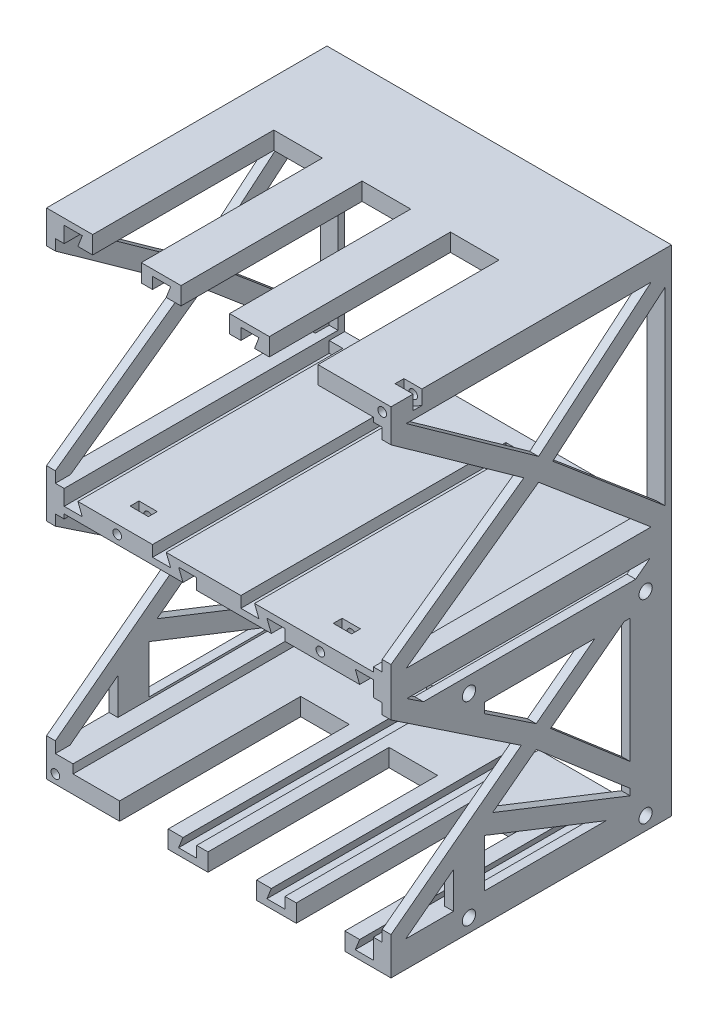
SolidWorks part; units mm, degrees
ref_plane "Front Plane" through (0, 0, 0) normal (0, 0, 1) x (1, 0, 0)
ref_plane "Top Plane" through (0, 0, 0) normal (0, 1, 0) x (1, 0, 0)
ref_plane "Right Plane" through (0, 0, 0) normal (1, 0, 0) x (0, 0, -1)
sketch "Bounds" plane through (0, 0, 0) normal (0, 0, 1) x (1, 0, 0)
  line L0 (-39, 56) -> (39, -56) construction
  line L1 (-39, 56) -> (39, 56)
  line L2 (-39, 56) -> (-39, -56)
  line L3 (-39, -56) -> (39, -56)
  line L4 (39, 56) -> (39, -56)
  line L5 (0, 50) -> (0, -50) construction
  line L6 (0, 0) -> (-66.1927, 0) construction
  line L7 (-35, 52) -> (35, 52)
  line L8 (35, 52) -> (35, -52)
  line L9 (-35, -52) -> (35, -52)
  line L10 (-35, 52) -> (-35, -52)
  dimension "D1" = 112
  dimension "D2" = 78
  dimension "D3" = 4
extrude "Boss-Extrude3" add sketch "Bounds" along normal blind 63.5
sketch "Sketch10" plane through (0, 0, 0) normal (0, 0, 1) x (1, 0, 0)
  line L0 (-26.7546, 0) -> (11.5824, 0) construction
  line L1 (-35, 2) -> (35, 2)
  line L2 (-35, 52) -> (-35, -52) construction
  line L3 (35, -52) -> (35, 52) construction
  line L4 (-35, -2) -> (35, -2)
  line L5 (35, 2) -> (35, -2)
  line L6 (-35, 2) -> (-35, -2)
  dimension "D1" = 2
extrude "Boss-Extrude4" add sketch "Sketch10" along normal up to surface (63.5 mm away) up to face at (0, 0, 63.5)
sketch "Placement" plane through (0, 0, 63.5) normal (0, 0, 1) x (1, 0, 0)
  line L0 (35, 2) -> (-35, 2) construction
  line L1 (-35, 52) -> (-15, 52)
  line L2 (-35, 52) -> (-35, 2)
  line L3 (-35, 2) -> (-15, 2)
  line L4 (-15, 52) -> (-15, 2)
  line L13 (-35, -52) -> (35, -52) construction
  line L14 (35, -2) -> (15, -2)
  line L15 (35, -2) -> (35, -52)
  line L16 (35, -52) -> (15, -52)
  line L17 (15, -2) -> (15, -52)
  line L26 (-15, 52) -> (-15, 2)
  line L27 (-15, 52) -> (5, 52)
  line L28 (5, 52) -> (5, 2)
  line L29 (-15, 2) -> (5, 2)
  line L30 (5, 52) -> (5, 2)
  line L31 (5, 52) -> (25, 52)
  line L32 (25, 52) -> (25, 2)
  line L33 (5, 2) -> (25, 2)
  line L34 (15, -2) -> (15, -52)
  line L35 (15, -2) -> (-5, -2)
  line L36 (-5, -2) -> (-5, -52)
  line L37 (15, -52) -> (-5, -52)
  line L38 (-5, -2) -> (-5, -52)
  line L39 (-5, -2) -> (-25, -2)
  line L40 (-25, -2) -> (-25, -52)
  line L41 (-5, -52) -> (-25, -52)
  dimension "D1" = 20
  dimension "D3" = 20
  dimension "D2" = 3
  dimension "D4" = 3
sketch "Sketch12" plane through (0, 0, 63.5) normal (0, 0, 1) x (1, 0, 0)
  line L0 (-35, 52) -> (-35, 54.6)
  line L1 (-35, 54.6) -> (-30.9, 54.6)
  line L2 (-30.9, 54.6) -> (-31.9, 52)
  line L3 (-35, 52) -> (-15, 52) construction
  line L4 (-31.9, 52) -> (-35, 52)
  line L5 (-35, 2) -> (-35, -0.51)
  line L6 (-35, -0.51) -> (-30.9, -0.51)
  line L7 (-30.9, -0.51) -> (-31.9, 2)
  line L8 (-35, 2) -> (-15, 2) construction
  line L9 (-31.9, 2) -> (-35, 2)
  line L10 (35, -2) -> (35, 0.51)
  line L11 (35, 0.51) -> (30.9, 0.51)
  line L12 (30.9, 0.51) -> (31.9, -2)
  line L13 (35, -2) -> (15, -2) construction
  line L14 (31.9, -2) -> (35, -2)
  line L15 (35, -52) -> (31.9, -52)
  line L17 (31.9, -52) -> (30.9, -54.51)
  line L18 (30.9, -54.51) -> (35, -54.51)
  line L19 (35, -54.51) -> (35, -52)
  line L20 (35, -52) -> (15, -52) construction
  line L21 (-15, 52) -> (-15, 54.6)
  line L22 (-15, 54.6) -> (-10.9, 54.6)
  line L23 (-10.9, 54.6) -> (-11.9, 52)
  line L24 (-11.9, 52) -> (-15, 52)
  line L25 (-15, 2) -> (-15, -0.51)
  line L26 (-15, -0.51) -> (-10.9, -0.51)
  line L27 (-10.9, -0.51) -> (-11.9, 2)
  line L28 (-11.9, 2) -> (-15, 2)
  line L29 (5, 52) -> (5, 54.6)
  line L30 (5, 54.6) -> (9.1, 54.6)
  line L31 (9.1, 54.6) -> (8.1, 52)
  line L32 (8.1, 52) -> (5, 52)
  line L33 (5, 2) -> (5, -0.51)
  line L34 (5, -0.51) -> (9.1, -0.51)
  line L35 (9.1, -0.51) -> (8.1, 2)
  line L36 (8.1, 2) -> (5, 2)
  line L37 (15, -2) -> (15, 0.51)
  line L38 (15, 0.51) -> (10.9, 0.51)
  line L39 (10.9, 0.51) -> (11.9, -2)
  line L40 (11.9, -2) -> (15, -2)
  line L41 (15, -52) -> (11.9, -52)
  line L42 (11.9, -52) -> (10.9, -54.51)
  line L43 (10.9, -54.51) -> (15, -54.51)
  line L44 (15, -54.51) -> (15, -52)
  line L45 (-5, -2) -> (-5, 0.51)
  line L46 (-5, 0.51) -> (-9.1, 0.51)
  line L47 (-9.1, 0.51) -> (-8.1, -2)
  line L48 (-8.1, -2) -> (-5, -2)
  line L49 (-5, -52) -> (-8.1, -52)
  line L50 (-8.1, -52) -> (-9.1, -54.51)
  line L51 (-9.1, -54.51) -> (-5, -54.51)
  line L52 (-5, -54.51) -> (-5, -52)
  dimension "D1" = 2.6
  dimension "D2" = 4.1
  dimension "D3" = 3.1
  dimension "D4" = 3.1
  dimension "D5" = 2.51
  dimension "D6" = 4.1
  dimension "D7" = 4.1
  dimension "D8" = 3.1
  dimension "D9" = 2.51
  dimension "D10" = 4.1
  dimension "D11" = 2.51
  dimension "D12" = 3.1
  dimension "D13" = 3
  dimension "D14" = 3
extrude "Cut-Extrude2" cut sketch "Sketch12" against normal offset from surface (60 mm away) 3.5 up to face at (0, -27, 0)
ref_plane "Plane2" through (0, 0, 1.5) normal (0, 0, 1) x (1, 0, 0)
sketch "Sketch13" plane through (0, 0, 1.5) normal (0, 0, 1) x (1, 0, 0)
  line L0 (-35, 2) -> (-15, 2) construction
  line L1 (-37, 51) -> (37, 51)
  line L2 (-37, 51) -> (-37, 3)
  line L3 (-37, 3) -> (37, 3)
  line L4 (37, 51) -> (37, 3)
  line L5 (-37, -3) -> (37, -3)
  line L6 (-37, -3) -> (-37, -50)
  line L7 (-37, -50) -> (37, -50)
  line L8 (37, -3) -> (37, -50)
  line L9 (-35, 52) -> (-15, 52) construction
  line L10 (-39, 56) -> (-39, -56) construction
  line L11 (35, 2) -> (35, 52) construction
  line L12 (-35, -2) -> (-35, -52) construction
  line L13 (39, -56) -> (39, 56) construction
  line L14 (-35, -52) -> (-8.1, -52) construction
  line L15 (-35, -2) -> (-8.1, -2) construction
  dimension "D1" = 1
  dimension "D2" = 1
  dimension "D3" = 2
  dimension "D4" = 2
  dimension "D5" = 2
  dimension "D6" = 2
  dimension "D7" = 2
  dimension "D8" = 1
extrude "Cut-Extrude3" cut sketch "Sketch13" along normal through all
sketch "Sketch14" plane through (0, 0, 0) normal (1, 0, 0) x (0, 0, -1)
  line L0 (-1.5, 27.0349) -> (-61.5, 27.0349) construction
  line L1 (-1.5, 51) -> (-63.5, 51)
  line L2 (-1.5, 51) -> (-1.5, 3)
  line L3 (-1.5, 3) -> (-63.5, 3)
  line L4 (-63.5, 51) -> (-63.5, 3)
  line L5 (-1.5, -25.0271) -> (-61.5, -25.0271) construction
  line L6 (-1.5, -3) -> (-63.5, -3)
  line L7 (-1.5, -3) -> (-1.5, -50)
  line L8 (-1.5, -50) -> (-63.5, -50)
  line L9 (-63.5, -3) -> (-63.5, -50)
  line L10 (-30.5571, 45) -> (-30.5571, -45) construction
  line L11 (-1.5, -3) -> (-30.5571, -25.0271) construction
  line L12 (-30.5571, -25.0271) -> (-63.5, -3) construction
  line L13 (-30.5571, -25.0271) -> (-1.5, -50) construction
  line L14 (-30.5571, -25.0271) -> (-63.5, -50) construction
  line L15 (-63.5, 51) -> (-29.9839, 27.0349) construction
  line L16 (-29.9839, 27.0349) -> (-1.5, 3) construction
  line L17 (-1.5, 51) -> (-29.9839, 27.0349) construction
  line L18 (-63.5, 3) -> (-29.9839, 27.0349) construction
  line L19 (-63.5, 48.5413) -> (-31.1472, 25.408)
  line L20 (-4.6066, 51) -> (-31.2715, 28.5652)
  line L21 (-31.2737, 25.5063) -> (-4.6013, 3)
  line L22 (-60.0681, 3) -> (-28.8184, 25.4096)
  line L23 (-60.0615, 51) -> (-28.8207, 28.6617)
  line L24 (-1.5, 48.3863) -> (-28.6963, 25.5045)
  line L25 (-28.6942, 28.5634) -> (-1.5, 5.6169)
  line L26 (-63.5, 5.4611) -> (-31.1495, 28.6601)
  line L27 (-62.3367, 52.6269) -> (-28.8207, 28.6617) construction
  line L28 (-64.6633, 49.3731) -> (-31.1472, 25.408) construction
  line L29 (-2.7876, 52.5304) -> (-31.2715, 28.5652) construction
  line L30 (-0.2124, 49.4696) -> (-28.6963, 25.5045) construction
  line L31 (-64.6655, 4.6253) -> (-31.1495, 28.6601) construction
  line L32 (-62.3345, 1.3747) -> (-28.8184, 25.4096) construction
  line L33 (-28.6942, 28.5634) -> (-0.2102, 4.5285) construction
  line L34 (-31.2737, 25.5063) -> (-2.7898, 1.4715) construction
  line L35 (-4.8107, -3) -> (-31.7653, -23.4333)
  line L36 (-29.4454, -23.3646) -> (-59.9018, -3)
  line L37 (-31.7653, -23.4333) -> (-63.5, -47.4903)
  line L38 (-31.8607, -26.5439) -> (-4.5684, -50)
  line L39 (-1.5, -5.5097) -> (-29.3489, -26.6209)
  line L40 (-31.6688, -26.6897) -> (-63.5, -5.4059)
  line L41 (-29.3489, -26.6209) -> (-60.1893, -50)
  line L42 (-29.2535, -23.5103) -> (-1.5, -47.3628)
  line L43 (-31.6688, -26.6897) -> (-64.6117, -4.6626) construction
  line L44 (-29.4454, -23.3646) -> (-62.3883, -1.3374) construction
  line L45 (-2.7082, -1.4062) -> (-31.7653, -23.4333) construction
  line L46 (-0.2918, -4.5938) -> (-29.3489, -26.6209) construction
  line L47 (-29.2535, -23.5103) -> (-0.1964, -48.4832) construction
  line L48 (-31.8607, -26.5439) -> (-2.8036, -51.5168) construction
  line L49 (-31.7653, -23.4333) -> (-64.7082, -48.4062) construction
  line L50 (-29.3489, -26.6209) -> (-62.2918, -51.5938) construction
  dimension "D1" = 2
  dimension "D2" = 2
  dimension "D3" = 2
  dimension "D4" = 2
extrude "Cut-Extrude4" cut sketch "Sketch14" against normal through all both and the other way through all contours L4 L26 L19 | L1 L23 L20 | L24 L25 L2 | L22 L3 L21 | L36 L35 L6 | L39 L42 L7 | L38 L41 L8 | L37 L40 L9 region at (0, 43.8549, 31.5839) region at (0, 27.0119, 9.96) region at (0, 27.0116, 53.4731) region at (0, 10.1674, 31.5844) region at (0, -9.5242, 31.7808) region at (0, -25.9991, 10.125) region at (0, -26.0085, 53.6675) region at (0, -42.5322, 31.7979)
sketch "Sketch15" plane through (0, 0, 63.5) normal (0, 0, 1) x (1, 0, 0)
  line L0 (39, 56) -> (-39, 56) construction
  line L1 (-28.55, 56) -> (-17.55, 56)
  line L2 (-28.55, 56) -> (-28.55, 52)
  line L3 (-28.55, 52) -> (-17.55, 52)
  line L4 (-17.55, 56) -> (-17.55, 52)
  line L5 (-15, 52) -> (-31.9, 52) construction
  line L6 (-35, 54.6) -> (-35, 51) construction
  line L7 (15, -52) -> (31.9, -52) construction
  line L8 (17.55, -52) -> (28.55, -52)
  line L9 (17.55, -52) -> (17.55, -56)
  line L10 (17.55, -56) -> (28.55, -56)
  line L11 (28.55, -52) -> (28.55, -56)
  line L12 (-39, -56) -> (39, -56) construction
  line L13 (35, -52) -> (35, -54.51) construction
  line M5 (39, 56) -> (-39, 56)
  line M13 (-31.9, 52) -> (-15, 52)
  dimension "D1" = 6.45
  dimension "D2" = 11
  dimension "D3" = 6.45
  dimension "D4" = 11
extrude "Cut-Extrude5" cut sketch "Sketch15" against normal blind 41 contours L4 L2 M5 M13 region at (-23.05, 54, 63.5)
extrude "Cut-Extrude6" cut sketch "Sketch15<4>" against normal blind 41 contours L10 L11 L8 L9
sketch "Sketch15<4>" plane through (0, 0, 63.5) normal (0, 0, 1) x (1, 0, 0) same geometry as "Sketch15"
pattern_linear "LPattern1" count 3 spacing 20 along (1, 0, 0) of "Cut-Extrude5"
pattern_linear "LPattern2" count 3 spacing 20 along (-1, 0, 0) of "Cut-Extrude6"
sketch "Sketch16" plane through (0, 0, 0) normal (1, 0, 0) x (0, 0, -1)
  line L0 (0, 0) -> (-91.3631, 0) construction
  line L1 (-31.75, 56) -> (-31.75, -56) construction
  line L4 (-63.5, 56) -> (0, 56) construction
  line L5 (-45.85, -9) -> (-5.85, -53) construction
  line L6 (-45.85, -9) -> (-5.85, -9) construction
  line L7 (-45.85, -9) -> (-45.85, -53) construction
  line L8 (-45.85, -53) -> (-5.85, -53) construction
  line L9 (-5.85, -9) -> (-5.85, -53) construction
  line L10 (0, -56) -> (0, 56) construction
  line L11 (-63.5, -56) -> (0, -56) construction
  point P6 (-31.75, 56)
  point P13 (-31.75, 0)
  dimension "D1" = 40
  dimension "D2" = 44
  dimension "D3" = 5.85
  dimension "D4" = 3
sketch "Sketch17" plane through (39, 0, 0) normal (1, 0, 0) x (0, 0, -1)
  line L13 (-49.35, -5.5) -> (-49.35, -56.5)
  line L18 (-49.35, -56.5) -> (-2.35, -56.5)
  line L19 (-2.35, -56.5) -> (-2.35, -5.5)
  line L20 (-2.35, -5.5) -> (-49.35, -5.5)
  line L21 (-49.35, -5.5) -> (-49.35, -56.5)
  line L22 (-49.35, -56.5) -> (-2.35, -56.5)
  line L23 (-2.35, -56.5) -> (-2.35, -5.5)
  line L24 (-2.35, -5.5) -> (-49.35, -5.5)
  line L25 (-42.35, -12.5) -> (-42.35, -49.5)
  line L26 (-42.35, -49.5) -> (-9.35, -49.5)
  line L27 (-9.35, -49.5) -> (-9.35, -12.5)
  line L28 (-9.35, -12.5) -> (-42.35, -12.5)
  line L29 (-42.35, -12.5) -> (-42.35, -49.5)
  line L30 (-42.35, -49.5) -> (-9.35, -49.5)
  line L31 (-9.35, -49.5) -> (-9.35, -12.5)
  line L32 (-9.35, -12.5) -> (-42.35, -12.5)
  line M17 (-30.6359, -27.5966) -> (-4.5684, -50)
  line M18 (-4.5684, -50) -> (-60.1893, -50)
  line M19 (-60.1893, -50) -> (-30.6359, -27.5966)
  line M23 (-1.5, -47.3628) -> (-27.3751, -25.1247)
  line M24 (-27.3751, -25.1247) -> (-1.5, -5.5097)
  line M39 (-30.6298, -22.5726) -> (-59.9018, -3)
  line M41 (-4.8107, -3) -> (-30.6298, -22.5726)
  dimension "D1" = 3.5
  dimension "D2" = 3.5
extrude "Boss-Extrude5" add sketch "Sketch17" against normal blind 2 contours L32 L24 L21 L29 M41 M39 | L32 L31 L23 M23 M24 | L31 L30 L29 L21 M19 M18 M17 region at (39, -8.8677, 30.8234) region at (39, -39.5027, 45.5674) region at (39, -26.1844, 5.6724)
sketch "Sketch18" plane through (39, 0, 0) normal (1, 0, 0) x (0, 0, -1)
  line L6 (-1.5, -47.3628) -> (-1.5, -5.5097)
  line L7 (-2.3923, -6.1861) -> (-2.35, -46.6323)
  line L8 (-2.35, -46.6323) -> (-1.5, -47.3628)
  line L9 (-2.3923, -6.1861) -> (-1.5, -5.5097)
  line L10 (-1.5, -5.5097) -> (-2.35, -6.1541) construction
  line L11 (-1.5, -5.5097) -> (-1.5, -47.3628) construction
extrude "Boss-Extrude6" add sketch "Sketch18" against normal blind 2
sketch "Sketch22" plane through (39, 0, 0) normal (1, 0, 0) x (0, 0, -1)
  line L0 (-49.35, -5.5) -> (-56.1629, -5.5)
  line L1 (-49.35, -10.0554) -> (-59.9018, -3) construction
  line L2 (-56.1629, -5.5) -> (-49.35, -10.0554)
  line L3 (-49.35, -10.0554) -> (-49.35, -5.5)
  line L4 (-42.35, -36.4766) -> (-9.35, -49.5)
  line L10 (-43.0842, -38.337) -> (-10.0842, -51.3604)
  line L11 (-41.6158, -34.6163) -> (-8.6158, -47.6396)
  line L12 (-42.35, -36.4766) -> (-40.4847, -35.0627)
  line L13 (-30.6359, -27.5966) -> (-42.35, -36.4766) construction
  line L14 (-42.35, -36.4766) -> (-42.35, -38.6268)
  line L15 (-42.35, -36.4766) -> (-42.35, -49.5) construction
  line L16 (-9.35, -49.5) -> (-9.35, -47.3499)
  line L17 (-9.35, -49.5) -> (-9.35, -45.8905) construction
  line L18 (-9.35, -49.5) -> (-14.7982, -49.5)
  line L19 (-42.35, -49.5) -> (-9.35, -49.5) construction
  line M4 (-49.35, -5.5) -> (-49.35, -10.0554)
  line M5 (-49.35, -10.0554) -> (-59.9018, -3)
  line M19 (-9.35, -45.8905) -> (-9.35, -49.5)
  line M20 (-9.35, -49.5) -> (-42.35, -49.5)
  line M21 (-42.35, -49.5) -> (-42.35, -36.4766)
  line M22 (-42.35, -36.4766) -> (-30.6359, -27.5966)
  dimension "D1" = 2
  dimension "D2" = 2
extrude "Boss-Extrude7" add sketch "Sketch22" against normal blind 2 contours L11 L4 M22 M19 | L10 L4 M21 M20 | L0 M4 M5 region at (39, -7.0185, 51.621) region at (39, -42.1059, 25.3882) region at (39, -43.5097, 27.1712)
sketch "Sketch24" plane through (0, 0, 1.5) normal (0, 0, 1) x (1, 0, 0)
  line L0 (35, -50) -> (35, -3) construction
  line L1 (35, -6) -> (37, -6)
  line L2 (35, -6) -> (35, -12)
  line L3 (35, -12) -> (37, -12)
  line L4 (37, -6) -> (37, -12)
  line L5 (37, -50) -> (37, -3) construction
  point P8 (35, -9)
  dimension "D1" = 6
extrude "Boss-Extrude9" add sketch "Sketch24" along normal blind 50
sketch "Sketch19" plane through (39, 0, 0) normal (1, 0, 0) x (0, 0, -1)
  circle A0 centre (-5.85, -9) radius 1.5
  circle A1 centre (-45.85, -9) radius 1.5
  circle A2 centre (-5.85, -53) radius 1.5
  circle A3 centre (-45.85, -53) radius 1.5
  dimension "D1" = 3
extrude "Cut-Extrude7" cut sketch "Sketch19" against normal blind 4
mirror "Mirror2" about plane through (0, 0, 0) normal (1, 0, 0) of "Cut-Extrude7", "Boss-Extrude9", "Boss-Extrude7", "Boss-Extrude6", "Boss-Extrude5"
sketch "Sketch25" plane through (0, 0, 63.5) normal (0, 0, 1) x (1, 0, 0)
  line L0 (-35, -52) -> (-22.45, -52) construction
  line L1 (-35, -50) -> (-33, -50)
  line L2 (-35, -50) -> (-35, -52)
  line L3 (-35, -52) -> (-33, -52)
  line L4 (-33, -50) -> (-33, -52)
  dimension "D1" = 2
extrude "Boss-Extrude10" add sketch "Sketch25" against normal up to surface (63.5 mm away) up to face at (0, -27, 0)
sketch "Sketch20" plane through (0, 0, 63.5) normal (0, 0, 1) x (1, 0, 0)
  line L0 (39, 56) -> (22.45, 56) construction
  line L2 (39, 48.5413) -> (39, 56) construction
  line L3 (39, -5.4059) -> (39, 5.4611) construction
  line L4 (-39, 5.4611) -> (-39, -5.4059) construction
  line L5 (-39, -47.4903) -> (-39, -56) construction
  line L6 (-39, -56) -> (-22.45, -56) construction
  circle A0 centre (37, 54) radius 0.975
  circle A1 centre (-37, -54) radius 0.975
  circle A2 centre (-23, 0) radius 0.975
  circle A3 centre (23, 0) radius 0.975
  dimension "D1" = 1.95
  dimension "D2" = 2
  dimension "D3" = 2
  dimension "D4" = 16
  dimension "D5" = 16
  dimension "D6" = 2
  dimension "D7" = 2
extrude "Cut-Extrude8" cut sketch "Sketch20" against normal blind 10
ref_plane "Plane3" through (0, 0, 58.5) normal (0, 0, 1) x (1, 0, 0)
sketch "Sketch21" plane through (0, 0, 58.5) normal (0, 0, 1) x (1, 0, 0)
  line L0 (37, 56.396) -> (34.925, 55.198)
  line L1 (34.925, 55.198) -> (34.925, 52.802)
  line L2 (34.925, 52.802) -> (37, 51.604)
  line L3 (37, 51.604) -> (39.075, 52.802)
  line L4 (39.075, 52.802) -> (39.075, 55.198)
  line L5 (39.075, 55.198) -> (37, 56.396)
  line L6 (37, 56.396) -> (37, 51.604) construction
  line L7 (39.075, 55.198) -> (39.075, 56.396)
  line L8 (39.075, 56.396) -> (34.925, 56.396)
  line L9 (34.925, 56.396) -> (34.925, 55.198)
  line L10 (23, 2.396) -> (20.925, 1.198)
  line L11 (20.925, 1.198) -> (20.925, -1.198)
  line L12 (20.925, -1.198) -> (23, -2.396)
  line L13 (23, -2.396) -> (25.075, -1.198)
  line L14 (25.075, -1.198) -> (25.075, 1.198)
  line L15 (25.075, 1.198) -> (23, 2.396)
  line L16 (23, 2.396) -> (23, -2.396) construction
  line L17 (25.075, 1.198) -> (25.075, 2.396)
  line L18 (25.075, 2.396) -> (20.925, 2.396)
  line L19 (20.925, 2.396) -> (20.925, 1.198)
  line L20 (-23, 2.396) -> (-25.075, 1.198)
  line L21 (-25.075, 1.198) -> (-25.075, -1.198)
  line L22 (-25.075, -1.198) -> (-23, -2.396)
  line L23 (-23, -2.396) -> (-20.925, -1.198)
  line L24 (-20.925, -1.198) -> (-20.925, 1.198)
  line L25 (-20.925, 1.198) -> (-23, 2.396)
  line L26 (-23, 2.396) -> (-23, -2.396) construction
  line L27 (-20.925, 1.198) -> (-20.925, 2.396)
  line L28 (-20.925, 2.396) -> (-25.075, 2.396)
  line L29 (-25.075, 2.396) -> (-25.075, 1.198)
  line L30 (-37, -51.604) -> (-39.075, -52.802)
  line L31 (-39.075, -52.802) -> (-39.075, -55.198)
  line L32 (-39.075, -55.198) -> (-37, -56.396)
  line L33 (-37, -56.396) -> (-34.925, -55.198)
  line L34 (-34.925, -55.198) -> (-34.925, -52.802)
  line L35 (-34.925, -52.802) -> (-37, -51.604)
  line L36 (-37, -51.604) -> (-37, -56.396) construction
  line L37 (-39.075, -55.198) -> (-39.075, -56.396)
  line L38 (-39.075, -56.396) -> (-34.925, -56.396)
  line L39 (-34.925, -56.396) -> (-34.925, -55.198)
  circle A0 centre (37, 54) radius 0.975 construction
  circle A1 centre (23, 0) radius 0.975 construction
  circle A2 centre (-23, 0) radius 0.975 construction
  circle A3 centre (-37, -54) radius 0.975 construction
  point P2 (37, 54)
  point P13 (23, 0)
  point P22 (-23, 0)
  point P35 (-37, -54)
  dimension "D1" = 4.15
  dimension "D2" = 4.15
  dimension "D3" = 120
  dimension "D4" = 4.15
  dimension "D5" = 120
  dimension "D6" = 4.15
  dimension "D7" = 120
  dimension "D8" = 4.15
  dimension "D9" = 120
extrude "Cut-Extrude9" cut sketch "Sketch21" against normal blind 2 contours L4 L5 L0 L1 L2 L3 | L7 L8 L5 | L8 L9 L0 | L24 L25 L20 L21 L22 L23 | L27 L28 L25 | L28 L29 L20 | L14 L15 L10 L11 L12 L13 | L18 L19 L10 | L17 L18 L15 | L34 L35 L30 L31 L32 L33 | L37 L38 L32 | L38 L39 L33 region at (37, 54, 58.5) region at (38.3833, 55.9967, 58.5) region at (35.6167, 55.9967, 58.5) region at (23, 0, 58.5) region at (24.3833, 1.9967, 58.5) region at (21.6167, 1.9967, 58.5) region at (-23, 0, 58.5) region at (-21.6167, 1.9967, 58.5) region at (-24.3833, 1.9967, 58.5) region at (-37, -54, 58.5) region at (-38.3833, -55.9967, 58.5) region at (-35.6167, -55.9967, 58.5)
sketch "Sketch26" plane through (0, 0, 0) normal (0, 0, -1) x (-1, 0, 0)
  line L0 (39, -56) -> (-39, -56) construction
  line L1 (-35, -52) -> (33, -52)
  line L2 (-35, -52) -> (-35, -56)
  line L3 (-35, -56) -> (33, -56)
  line L4 (33, -52) -> (33, -56)
extrude "Cut-Extrude10" cut sketch "Sketch26" against normal blind 6
